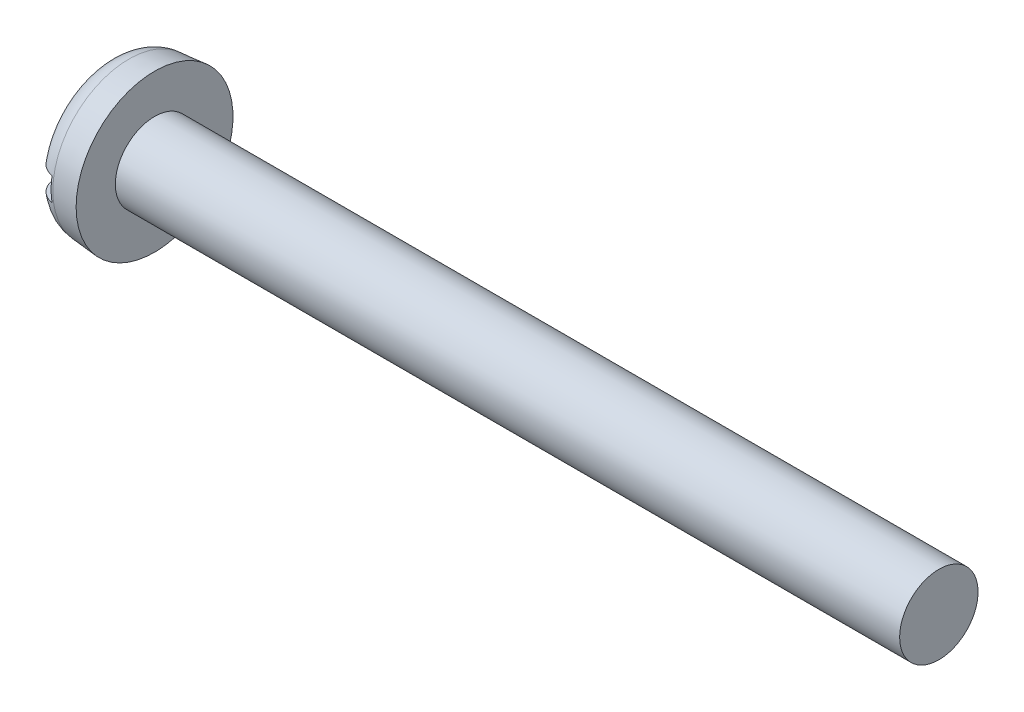
SolidWorks part; units mm, degrees
ref_plane "Plane1" through (0, 0, 0) normal (0, 0, 1) x (1, 0, 0)
ref_plane "Plane2" through (0, 0, 0) normal (0, 1, 0) x (1, 0, 0)
ref_plane "Plane3" through (0, 0, 0) normal (1, 0, 0) x (0, 0, -1)
sketch "BodySke" plane through (0, 0, 0) normal (0, 0, 1) x (1, 0, 0)
  line L0 (2.4, 2) -> (2.4, 4)
  line L1 (0, 0) -> (0, 3.79)
  line L2 (-25.4, 0) -> (127, 0) construction
  line L3 (42.4, 0) -> (0, 0)
  line L4 (2.4, 2) -> (42.4, 2)
  line L5 (42.4, 2) -> (42.4, 0)
  line L6 (0, 3.79) -> (2.4, 4)
  line L9 (3.1, 3.5875) -> (3.1, -5.9375) construction
  line L10 (2.4, 6.35) -> (2.4, -3.175) construction
  dimension "Length" = 40
  dimension "Head_ht" = 2.4
  dimension "Head_dia" = 8
  dimension "Diameter" = 4
revolve "Base-Revolve" add sketch "BodySke"
cosmetic thread "ThreadCosmetic"
fillet "Fillet1" [suppressed] radius 0.2
fillet "Fillet2" radius 1.2 1 edges at (0, 0, 3.79)
sketch "Sketch2" plane through (0, 0, 0) normal (1, 0, 0) x (0, 0, -1)
  line L0 (4, -0.6) -> (-4, -0.6)
  line L1 (4, -0.6) -> (4, 0.6)
  line L2 (-4, 0.6) -> (4, 0.6)
  line L3 (-4, 0.6) -> (-4, -0.6)
  dimension "D1" = 8
  dimension "D2" = 4
  dimension "D3" = 0.6
extrude "Slot" cut sketch "Sketch2" along normal blind 1
sketch "ThdSchSke" plane through (0, 0, 0) normal (0, 0, 1) x (1, 0, 0)
  line L0 (3.8, -1.61) -> (3.5269, -2)
  line L1 (3.8, -1.61) -> (4.0731, -2)
  line L2 (4.0731, -2) -> (4.0731, -2.5)
  line L3 (-3.175, 0) -> (5.1513, 0) construction
  line L5 (4.0731, -2.5) -> (3.5269, -2.5)
  line L6 (3.5269, -2.5) -> (3.5269, -2)
  dimension "Diameter" = 4
  dimension "Thread_minor" = 3.22
  dimension "Start" = 3.8
revolve "ThreadSchematic" [suppressed] cut sketch "ThdSchSke" angle 360 about L3
pattern_linear "ThdSchPat" [suppressed]
ref_axis "Axis1" through (27.6692, 0, 0) along (-1, 0, 0)
equation "\"D1@Sketch2\" = \"Head_dia@BodySke\""
equation "\"D2@Sketch2\" = \"D1@Sketch2\" / 2"
equation "\"D3@Sketch2\" = \"Slot_width@Sketch2\" / 2"
equation "\"Thread_length@ThreadCosmetic\" = ((sgn( (\"Length@BodySke\" - \"Advance@BodySke\" * 2.0 ) - \"Thread_nom@BodySke\" )-1)*( (\"Length@BodySke\" - \"Advance@BodySke\"  * 2.0) - \"Thread_nom@BodySke\" ))/-2+ \"Thread_nom@BodySke\""
equation "\"Thread_minor@ThdSchSke\" = \"Thread_minor@ThreadCosmetic\""
equation "\"Diameter@ThdSchSke\" = \"Diameter@BodySke\""
equation "\"Overcut@ThdSchSke\" = \"Diameter@BodySke\" * 1.25"
equation "\"Start@ThdSchSke\" = \"Head_ht@BodySke\" + \"Length@BodySke\" - \"Thread_length@ThreadCosmetic\"  '---Non-countersunk---"
equation "\"Num_threads@ThdSchPat\" = int( \"Thread_length@ThreadCosmetic\" / \"Advance@BodySke\" + 0.999 )  + 1"
equation "\"Advance@ThdSchPat\" = \"Thread_length@ThreadCosmetic\" /  (\"Num_threads@ThdSchPat\" - 1) 'relax it"
